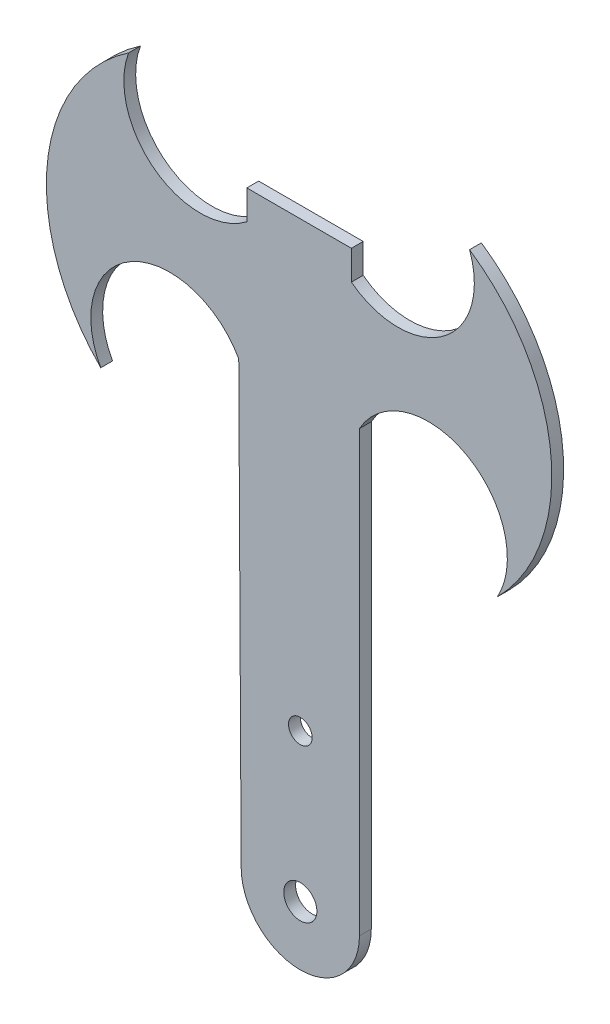
SolidWorks part; units mm, degrees
ref_plane "Alzado" through (0, 0, 0) normal (0, 0, 1) x (1, 0, 0)
ref_plane "Planta" through (0, 0, 0) normal (0, 1, 0) x (1, 0, 0)
ref_plane "Vista lateral" through (0, 0, 0) normal (1, 0, 0) x (0, 0, -1)
sketch "Model" plane through (0, 0, 0) normal (0, 0, 1) x (1, 0, 0)
  line L0 (40, 21.3839) -> (40.206, -15.7616)
  line L1 (50.206, -15.7616) -> (50.206, 21.3839)
  line L2 (49.524, 31.7633) -> (49.524, 34.2437)
  line L3 (49.524, 34.2437) -> (40.682, 34.2437)
  line L4 (40.682, 34.2437) -> (40.682, 31.7633)
  circle A0 centre (45.206, -15.7616) radius 1.4
  circle A1 centre (45.206, -3.2616) radius 1
  arc A2 (40, 21.3839) -> (28.3343, 14.8971) centre (34.1671, 18.1405) ccw
  arc A3 (40.206, -15.7616) -> (50.206, -15.7616) centre (45.206, -15.7616) ccw
  arc A4 (61.8717, 14.8971) -> (50.206, 21.3839) centre (56.0388, 18.1405) ccw
  arc A5 (61.8717, 14.8971) -> (59.5165, 39.1372) centre (50.6665, 26.0429) ccw
  arc A6 (49.524, 31.7633) -> (59.5165, 39.1372) centre (53.4615, 36.885) ccw
  arc A7 (30.6895, 39.1372) -> (40.682, 31.7633) centre (36.7445, 36.885) ccw
  arc A8 (30.6895, 39.1372) -> (28.3343, 14.8971) centre (39.5395, 26.0429) ccw
base flange "Brida base1" sketch "Model" thickness 1 reverse thickness direction no parameters "D1"=0.7366
sketch "Líneas de pliegue1" [suppressed] plane through (0, 0, 0) normal (0, 1, 0) x (1, 0, 0)
sketch "Cuadro delimitador1" [suppressed] plane through (0, 0, 0) normal (0, 1, 0) x (1, 0, 0)
sheet metal parameters "Chapa metálica1" thickness 1 parameters "D1"=0.7366
flat pattern "Chapa desplegada1" [suppressed]
sketch "Líneas de pliegue2" plane through (0, 0, 0) normal (0, 1, 0) x (1, 0, 0)
sketch3d "Cuadro delimitador2" [suppressed]
  line L0 (-32.3039, 20.9968, 0) -> (-32.3039, -38.9018, 0) construction
  line L1 (10.4322, 20.9968, 0) -> (10.4322, -38.9018, 0) construction
  line L2 (-32.3039, 20.9968, 0) -> (10.4322, 20.9968, 0) construction
  line L3 (-32.3039, -38.9018, 0) -> (10.4322, -38.9018, 0) construction
